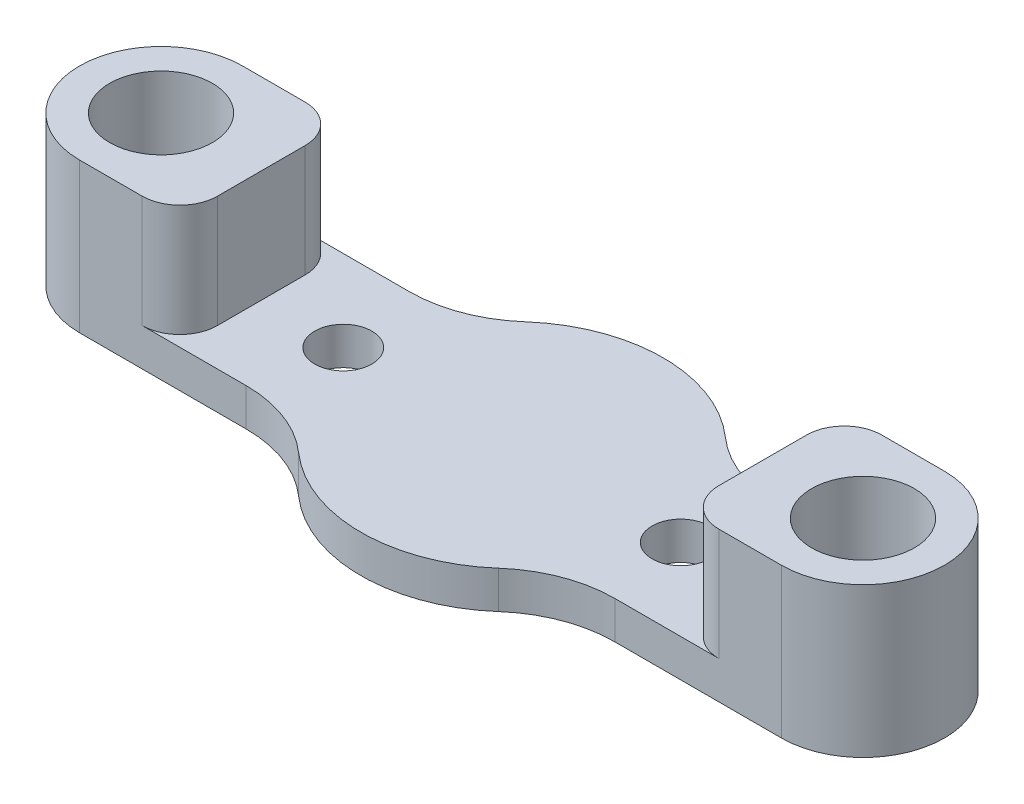
SolidWorks part; units mm, degrees
material "Custom Plastic"
ref_plane "Front Plane" through (0, 0, 0) normal (0, 0, 1) x (1, 0, 0)
ref_plane "Top Plane" through (0, 0, 0) normal (0, 1, 0) x (1, 0, 0)
ref_plane "Right Plane" through (0, 0, 0) normal (1, 0, 0) x (0, 0, -1)
sketch "Sketch1" plane through (0, 0, 0) normal (0, 1, 0) x (1, 0, 0)
  line L0 (-1000, 0) -> (49000, 0) construction
  line L1 (0, -1000) -> (0, 49000) construction
  line L2 (-7.3514, 3.25) -> (-14, 3.25)
  line L3 (-7.3514, -3.25) -> (-14, -3.25)
  line L4 (7.3514, -3.25) -> (14, -3.25)
  line L5 (7.3514, 3.25) -> (14, 3.25)
  circle A1 centre (-6.73, 0) radius 1.14
  arc A5 (3.99, 4.5211) -> (-3.99, 4.5211) centre (0, 0) ccw
  arc A6 (-7.3514, 3.25) -> (-3.99, 4.5211) centre (-7.3514, 8.33) ccw
  circle A17 centre (-14, 0) radius 2.05
  arc A18 (-14, 3.25) -> (-14, -3.25) centre (-14, 0) ccw
  arc A19 (3.99, -4.5211) -> (-3.99, -4.5211) centre (0, 0) cw
  arc A20 (-7.3514, -3.25) -> (-3.99, -4.5211) centre (-7.3514, -8.33) cw
  arc A21 (7.3514, 3.25) -> (3.99, 4.5211) centre (7.3514, 8.33) cw
  arc A22 (7.3514, -3.25) -> (3.99, -4.5211) centre (7.3514, -8.33) ccw
  circle A23 centre (6.73, 0) radius 1.14
  circle A24 centre (14, 0) radius 2.05
  arc A25 (14, 3.25) -> (14, -3.25) centre (14, 0) cw
  point P12 (-7.87, 2.917)
  point P19 (-7.1567, 2.7572)
  point P24 (-7.1567, 2.7572)
  dimension "D1" = 6.03
  dimension "D3" = 2.28
  dimension "D4" = 5.08
  dimension "D6" = 4.1
  dimension "D8" = 6.5
  dimension "D2" = 13.46
  dimension "D7" = 28
extrude "Boss-Extrude2" add sketch "Sketch1" along normal blind 1.5
sketch "Sketch2" plane through (0, 1.5, 0) normal (0, 1, 0) x (1, 0, 0)
  line L0 (0, -1000) -> (0, 49000) construction
  line L1 (-14, 3.25) -> (-10, 3.25)
  line L2 (-7.3514, 3.25) -> (-14, 3.25) construction
  line L3 (-10, 3.25) -> (-10, -3.25)
  line L4 (-14, -3.25) -> (-7.3514, -3.25) construction
  line L5 (-10, -3.25) -> (-14, -3.25)
  line L6 (10, -3.25) -> (14, -3.25)
  line L7 (10, 3.25) -> (10, -3.25)
  line L8 (14, 3.25) -> (10, 3.25)
  arc A0 (-14, 3.25) -> (-14, -3.25) centre (-14, 0) ccw
  circle A2 centre (-14, 0) radius 2.05 construction
  circle A3 centre (-14, 0) radius 2.05
  circle A4 centre (14, 0) radius 2.05
  arc A5 (14, 3.25) -> (14, -3.25) centre (14, 0) cw
  dimension "D1" = 4
extrude "Boss-Extrude3" add sketch "Sketch2" along normal blind 4.47
fillet "Fillet1" radius 1.5 4 edges at (10, 3.735, 3.25) (10, 3.735, -3.25) (-10, 3.735, 3.25) (-10, 3.735, -3.25)
